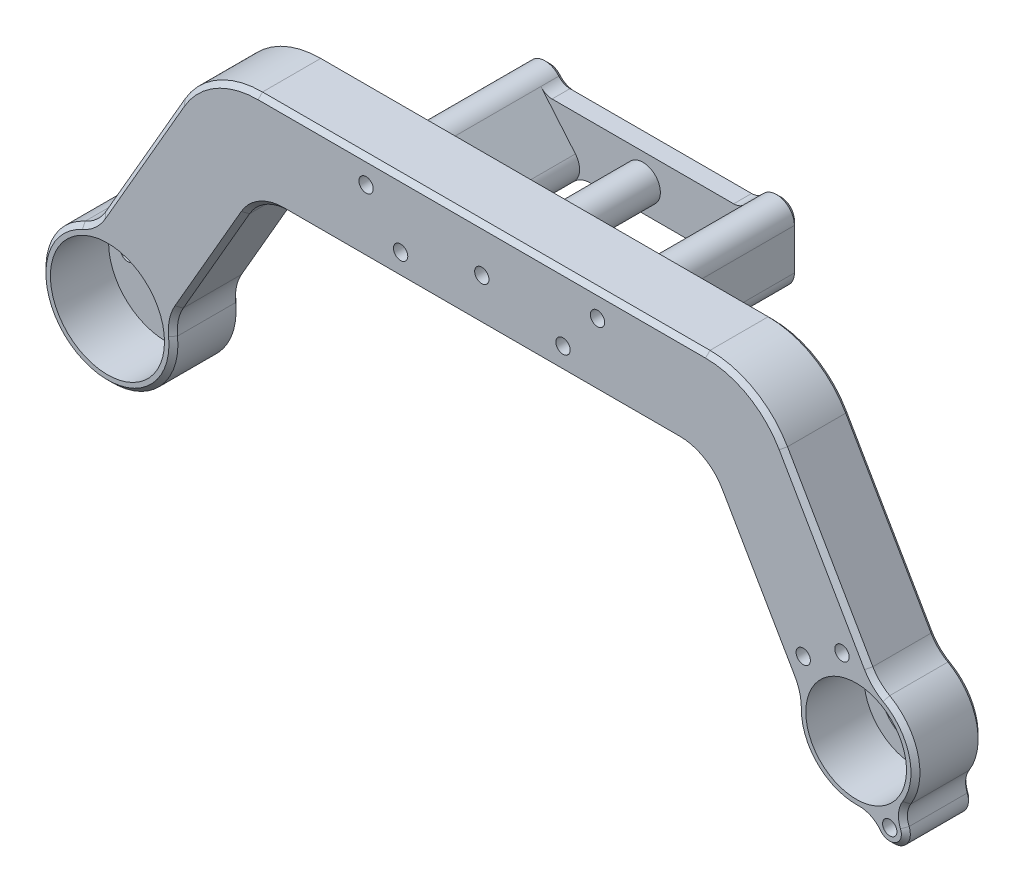
SolidWorks part; units mm, degrees
other "Markup1"
sketch "Sketch2"
ref_plane "Front Plane" through (0, 0, 0) normal (0, 0, 1) x (1, 0, 0)
ref_plane "Top Plane" through (0, 0, 0) normal (0, 1, 0) x (1, 0, 0)
ref_plane "Right Plane" through (0, 0, 0) normal (1, 0, 0) x (0, 0, -1)
ref_axis "X" through (-88.99, 0, 0) along (1, 0, 0)
ref_axis "Y" through (0, 55, 0) along (0, -1, 0)
ref_axis "Z" through (0, 0, -88.99) along (0, 0, 1)
sketch "Sketch1" plane through (0, 0, 0) normal (0, 0, 1) x (1, 0, 0)
  line L0 (0, 10) -> (0, -10) construction
  line L1 (-50, 10) -> (50, 10)
  line L2 (-50, -10) -> (50, -10)
  line L3 (67.3205, 0) -> (92.3205, -43.3013)
  line L4 (75, -53.3013) -> (50, -10)
  line L5 (-75, -53.3013) -> (-50, -10)
  line L6 (-67.3205, 0) -> (-92.3205, -43.3013)
  arc A0 (50, 10) -> (67.3205, 0) centre (50, -10) cw
  arc A1 (92.3205, -43.3013) -> (75, -53.3013) centre (83.6603, -48.3013) cw
  arc A3 (-92.3205, -43.3013) -> (-75, -53.3013) centre (-83.6603, -48.3013) ccw
  arc A4 (-50, 10) -> (-67.3205, 0) centre (-50, -10) ccw
  point P4 (0, 0)
  dimension "D1" = 20
  dimension "D2" = 50
  dimension "D3" = 60
  dimension "D4" = 50
extrude "Boss-Extrude1" add sketch "Sketch1" along normal mid plane 15
ref_plane "Plane1" through (0, 0, 28.5) normal (0, 0, 1) x (1, 0, 0)
sketch "Sketch3" plane through (0, 0, 0) normal (0, 0, 1) x (1, 0, 0)
  line L0 (-22, 0) -> (22, 0) construction
  line L1 (25.8567, 4.5963) -> (18.1433, -4.5963) construction
  line L2 (0, 0) -> (0, 1.6) construction
  line L3 (-25.8567, 4.5963) -> (-18.1433, -4.5963) construction
  circle A1 centre (0, 0) radius 1.6
  circle A2 centre (25.8567, 4.5963) radius 1.6
  circle A3 centre (18.1433, -4.5963) radius 1.6
  circle A4 centre (-25.8567, 4.5963) radius 1.6
  circle A5 centre (-18.1433, -4.5963) radius 1.6
  point P7 (0, 0)
  point P10 (22, 0)
  dimension "D6" = 3.2
  dimension "D3" = 12
  dimension "D4" = 22
  dimension "D5" = 50
extrude "Cut-Extrude1" cut sketch "Sketch3" against normal through all both and the other way through all
sketch "Sketch4" plane through (0, 0, 28.5) normal (0, 0, 1) x (1, 0, 0)
  line L0 (25.8567, 4.5963) -> (18.1433, -4.5963) construction
  line L1 (-25.8567, 4.5963) -> (-18.1433, -4.5963) construction
  line L2 (25.8567, 4.5963) -> (18.1433, -4.5963) construction
  line L3 (-25.8567, 4.5963) -> (-18.1433, -4.5963) construction
  line L4 (15.0791, -2.0251) -> (22.7925, 7.1674)
  line L5 (29.8567, 4.5963) -> (29.8567, -4.5963)
  line L6 (25.8567, -8.5963) -> (18.1433, -8.5963)
  line L7 (0, 0) -> (0, 1.6) construction
  line L8 (0, 0) -> (0, 1.6) construction
  line L9 (-25.8567, -8.5963) -> (-18.1433, -8.5963)
  line L10 (-29.8567, 4.5963) -> (-29.8567, -4.5963)
  line L11 (-15.0791, -2.0251) -> (-22.7925, 7.1674)
  line L12 (20.289, 6) -> (-20.289, 6)
  line L13 (0, 6) -> (0, 3.9)
  line L14 (0, -3.9) -> (0, -6)
  line L15 (-11.8193, -6) -> (11.8193, -6)
  circle A0 centre (25.8567, 4.5963) radius 1.6 construction
  circle A1 centre (18.1433, -4.5963) radius 1.6 construction
  circle A2 centre (-25.8567, 4.5963) radius 1.6 construction
  circle A3 centre (-18.1433, -4.5963) radius 1.6 construction
  circle A4 centre (0, 0) radius 1.6 construction
  circle A5 centre (25.8567, 4.5963) radius 1.6
  circle A6 centre (18.1433, -4.5963) radius 1.6
  circle A7 centre (-25.8567, 4.5963) radius 1.6
  circle A8 centre (-18.1433, -4.5963) radius 1.6
  circle A9 centre (0, 0) radius 1.6
  arc A10 (22.7925, 7.1674) -> (29.8567, 4.5963) centre (25.8567, 4.5963) cw
  arc A11 (29.8567, -4.5963) -> (25.8567, -8.5963) centre (25.8567, -4.5963) cw
  arc A12 (18.1433, -8.5963) -> (15.0791, -2.0251) centre (18.1433, -4.5963) cw
  arc A13 (-29.8567, -4.5963) -> (-25.8567, -8.5963) centre (-25.8567, -4.5963) ccw
  arc A14 (-22.7925, 7.1674) -> (-29.8567, 4.5963) centre (-25.8567, 4.5963) ccw
  arc A15 (-18.1433, -8.5963) -> (-15.0791, -2.0251) centre (-18.1433, -4.5963) ccw
  circle A16 centre (0, 0) radius 3.9
  arc A17 (22.7925, 7.1674) -> (20.289, 6) centre (20.289, 9.2681) cw
  arc A18 (11.8193, -6) -> (15.3326, -7.4424) centre (11.8193, -11) cw
  arc A19 (-11.8193, -6) -> (-15.3326, -7.4424) centre (-11.8193, -11) ccw
  arc A20 (-22.7925, 7.1674) -> (-20.289, 6) centre (-20.289, 9.2681) ccw
  dimension "D1" = 4
  dimension "D4" = 4
  dimension "D5" = 7.8
  dimension "D6" = 12
  dimension "D7" = 5
  dimension "D2" = 4
  dimension "D3" = 4
extrude "Boss-Extrude2" add sketch "Sketch4" against normal up to surface (21 mm away) separate body contours L9 A15 L11 A14 L10 A13 A8 A7 | A12 L6 A11 L5 A10 L4 A6 A5 | A16 A9 region at (23.3022, -1.3358, 28.5) region at (2.6797, 2.6797, 28.5) region at (-23.3022, -1.3358, 28.5) up to face at (-19.7433, -4.5963, 7.5)
extrude "Boss-Extrude3" add sketch "Sketch4<3>" along normal blind 5 contours L9 A15 L11 A14 L10 A13 A8 A7 | A20 L11 A15 A19 L15 L14 A16 L13 L12 | A16 A9 | L15 A18 A12 L4 A17 L12 L13 A16 L14 | A12 L6 A11 L5 A10 L4 A6 A5 region at (9.702, 0.5432, 28.5) region at (23.3022, -1.3358, 28.5) region at (-9.702, 0.5432, 28.5) region at (2.6797, 2.6797, 28.5) region at (-23.3022, -1.3358, 28.5)
sketch "Sketch4<3>" plane through (0, 0, 28.5) normal (0, 0, 1) x (1, 0, 0) same geometry as "Sketch4"
chamfer "Chamfer1" distance 1 angle 45 16 edges at (22, -8.5963, 33.5) (28.6852, -7.4247, 33.5) (16.6241, -8.2966, 33.5) (29.8567, 0, 33.5) (13.7183, -6.3746, 33.5) (27.2248, 8.355, 33.5) (0, -6, 33.5) (21.6702, 6.3062, 33.5) (-13.7183, -6.3746, 33.5) (0, 6, 33.5) (-16.6241, -8.2966, 33.5) (-21.6702, 6.3062, 33.5) (-22, -8.5963, 33.5) (-27.2248, 8.355, 33.5) (-28.6852, -7.4247, 33.5) (-29.8567, 0, 33.5)
sketch "Sketch5" plane through (0, 0, 0) normal (0, 0, 1) x (1, 0, 0)
  line L0 (-92.1603, -48.3013) -> (-75.1603, -48.3013) construction
  circle A1 centre (83.6603, -48.3013) radius 13.25
  circle A3 centre (83.6603, -48.3013) radius 11.25
  circle A4 centre (83.6603, -48.3013) radius 7.5
  circle A5 centre (-83.6603, -48.3013) radius 12.75
  circle A6 centre (-83.6603, -48.3013) radius 14.75
  circle A7 centre (-83.6603, -48.3013) radius 5.5
  circle A8 centre (-75.1603, -48.3013) radius 1.6
  circle A9 centre (-92.1603, -48.3013) radius 1.6
  point P14 (-83.6603, -48.3013)
  dimension "D1" = 2
  dimension "D2" = 22.5
  dimension "D3" = 15
  dimension "D4" = 25.5
  dimension "D6" = 11
  dimension "D8" = 3.2
  dimension "D7" = 17
  dimension "D5" = 2
extrude "Boss-Extrude4" add sketch "Sketch5" along normal up to surface and the other way up to surface contours A1 A3 region at (70.785, -48.3013, 0) up to face at (-19.7433, -4.5963, 7.5) other way up to face at (-19.7433, -4.5963, -7.5)
extrude "Cut-Extrude2" cut sketch "Sketch5<3>" against normal through all both and the other way through all contours A3
sketch "Sketch5<3>" plane through (0, 0, 0) normal (0, 0, 1) x (1, 0, 0) same geometry as "Sketch5"
extrude "Boss-Extrude5" add sketch "Sketch5<4>" against normal blind 2 from surface contours A3 A4 region at (72.7285, -48.3013, 0) starting at face at (72.4103, -48.3013, 7.5)
sketch "Sketch5<4>" plane through (0, 0, 0) normal (0, 0, 1) x (1, 0, 0) same geometry as "Sketch5"
extrude "Cut-Extrude3" cut sketch "Sketch5<5>" against normal through all both and the other way through all contours A5
sketch "Sketch5<5>" plane through (0, 0, 0) normal (0, 0, 1) x (1, 0, 0) same geometry as "Sketch5"
extrude "Boss-Extrude6" add sketch "Sketch5<6>" along normal up to surface (7.5 mm away) and the other way up to surface (7.5 mm away) contours A6 A5 region at (-97.9931, -48.3013, 0) up to face at (1.2608, -17.4619, 7.5) other way up to face at (1.2608, -17.4619, -7.5)
sketch "Sketch5<6>" plane through (0, 0, 0) normal (0, 0, 1) x (1, 0, 0) same geometry as "Sketch5"
extrude "Boss-Extrude7" add sketch "Sketch5<7>" against normal blind 2 from surface contours A5 A9 A7 A8 region at (-96.0496, -48.3013, 0) starting at face at (0.0325, -19.5895, 7.5)
sketch "Sketch5<7>" plane through (0, 0, 0) normal (0, 0, 1) x (1, 0, 0) same geometry as "Sketch5"
fillet "Fillet1" radius 10 6 edges at (87.9742, -35.7732, 0) (70.6537, -45.7732, 0) (-86.8992, -33.9113, 0) (-69.5787, -43.9113, 0) (50, -10, 0) (-50, -10, 0)
sketch "Sketch6" plane through (0, 0, 0) normal (0, 0, 1) x (1, 0, 0)
  line L0 (71.8301, -37.8109) -> (80.4904, -32.8109) construction
  line L1 (76.1603, -35.3109) -> (83.6603, -48.3013) construction
  line L2 (83.6603, -48.3013) -> (91.1603, -61.2917) construction
  line L3 (75, -53.3013) -> (50, -10) construction
  circle A0 centre (91.1603, -61.2917) radius 1.6
  circle A1 centre (80.4904, -32.8109) radius 1.6
  circle A2 centre (71.8301, -37.8109) radius 1.6
  arc A3 (88.3078, -63.488) -> (94.4885, -59.9195) centre (91.1603, -61.2917) ccw
  arc A4 (94.4885, -59.9195) -> (94.878, -55.3529) centre (99.1111, -58.0138) cw
  circle A5 centre (83.6603, -48.3013) radius 13.25 construction
  arc A6 (88.3078, -63.488) -> (84.1582, -61.5419) centre (84.3462, -66.5384) ccw
  arc A7 (84.1582, -61.5419) -> (94.878, -55.3529) centre (83.6603, -48.3013) ccw
  dimension "D4" = 3.2
  dimension "D5" = 2
  dimension "D6" = 5
  dimension "D1" = 10
  dimension "D2" = 15
  dimension "D3" = 15
extrude "Boss-Extrude8" add sketch "Sketch6" along normal up to surface (7.5 mm away) and the other way up to surface (7.5 mm away) contours A7 A6 A3 A4 A0 region at (86.5301, -61.8816, 0) up to face at (0.1801, -23.435, 7.5) other way up to face at (0.1801, -23.435, -7.5)
extrude "Cut-Extrude4" cut sketch "Sketch6<3>" against normal through all both and the other way through all contours A2 | A1 | A0 region at (91.1603, -61.2917, 0) region at (80.4904, -32.8109, 0) region at (71.8301, -37.8109, 0)
sketch "Sketch6<3>" plane through (0, 0, 0) normal (0, 0, 1) x (1, 0, 0) same geometry as "Sketch6"
sketch "Sketch7" plane through (0, 0, 0) normal (0, 0, 1) x (1, 0, 0)
  circle A0 centre (80.4904, -32.8109) radius 3
  circle A1 centre (71.8301, -37.8109) radius 3
  circle A2 centre (91.1603, -61.2917) radius 3
  dimension "D1" = 6
extrude "Cut-Extrude5" cut sketch "Sketch7" against normal blind 3.5 from surface starting at face at (70.2301, -37.8109, 7.5)
chamfer "Chamfer2" distance 1 angle 45 38 edges at (0, -10, -7.5) (49.2265, -11.3397, -7.5) (-49.2265, -11.3397, -7.5) (60.9794, -29.0169, -7.5) (-60.2985, -27.8375, -7.5) (70.0858, -45.5012, -7.5) (-68.8331, -43.6037, -7.5) (-91.0353, -61.0751, -7.5) (88.0225, -35.1454, -7.5) (-87.0056, -33.1118, -7.5) (76.8565, -16.5169, -7.5) (-76.1756, -15.3375, -7.5) (60, 7.3205, -7.5) (-60, 7.3205, -7.5) (0, 10, -7.5) (0, -10, 7.5) (49.2265, -11.3397, 7.5) (-49.2265, -11.3397, 7.5) (60.9794, -29.0169, 7.5) (-60.2985, -27.8375, 7.5) (70.0858, -45.5012, 7.5) (-68.8331, -43.6037, 7.5) (-91.0353, -61.0751, 7.5) (88.0225, -35.1454, 7.5) (-87.0056, -33.1118, 7.5) (76.8565, -16.5169, 7.5) (-76.1756, -15.3375, 7.5) (60, 7.3205, 7.5) (-60, 7.3205, 7.5) (0, 10, 7.5) (86.4692, -62.0115, -7.5) (92.9603, -64.4093, -7.5) (94.1292, -57.5889, -7.5) (96.5024, -45.0391, -7.5) (74.4141, -57.7918, 7.5) (86.4692, -62.0115, 7.5) (92.9603, -64.4093, 7.5) (94.1292, -57.5889, 7.5)
mirror "Mirror1" about plane through (0, 0, 0) normal (0, 0, 1) of bodies 115 106
delete or keep bodies "Body-Delete/Keep 1" type keep bodies bodies 117 116
